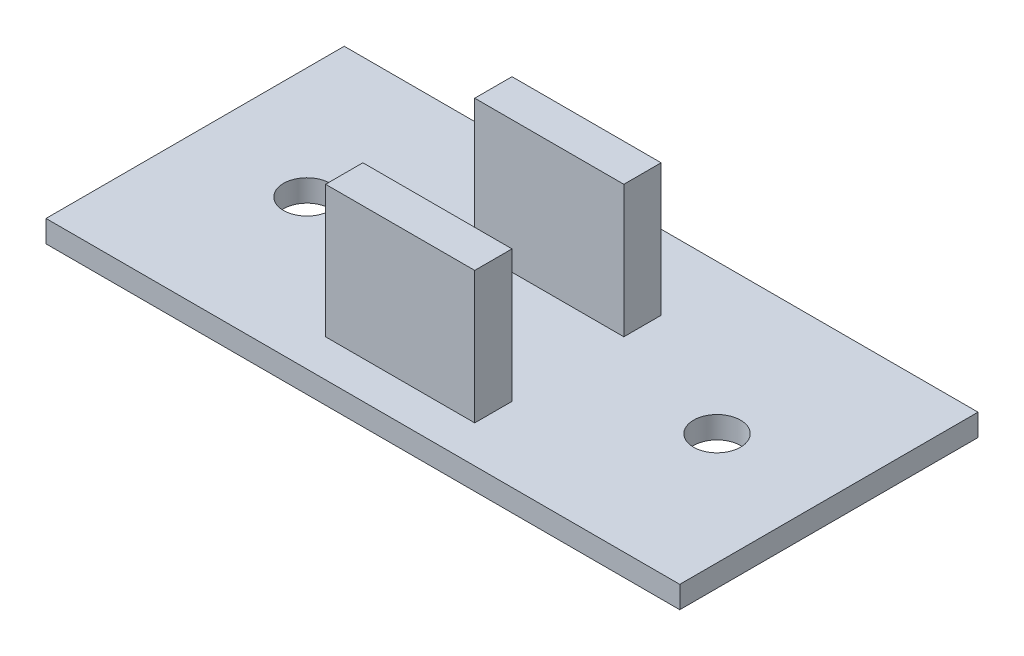
SolidWorks part; units mm, degrees
ref_plane "Front Plane" through (0, 0, 0) normal (0, 0, 1) x (1, 0, 0)
ref_plane "Top Plane" through (0, 0, 0) normal (0, 1, 0) x (1, 0, 0)
ref_plane "Right Plane" through (0, 0, 0) normal (1, 0, 0) x (0, 0, -1)
sketch "Sketch1" plane through (0, 0, 0) normal (0, 1, 0) x (1, 0, 0)
  line L0 (0, 10.16) -> (43.18, 10.16) construction
  line L1 (0, 0) -> (43.18, 0)
  line L2 (0, 0) -> (0, 20.32)
  line L3 (0, 20.32) -> (43.18, 20.32)
  line L4 (43.18, 0) -> (43.18, 20.32)
  line L5 (21.59, 20.32) -> (21.59, 0) construction
  circle A0 centre (7.62, 10.16) radius 1.6
  circle A1 centre (35.56, 10.16) radius 1.6
  dimension "D4" = 3.2
  dimension "D1" = 43.18
  dimension "D2" = 20.32
  dimension "D3" = 7.62
extrude "Boss-Extrude1" add sketch "Sketch1" along normal blind 1.5
sketch "Sketch2" plane through (0, 1.5, 0) normal (0, 1, 0) x (1, 0, 0)
  line L0 (0, 0) -> (43.18, 0) construction
  line L1 (16.51, 5.08) -> (26.67, 5.08)
  line L2 (16.51, 5.08) -> (16.51, 2.54)
  line L3 (16.51, 2.54) -> (26.67, 2.54)
  line L4 (26.67, 5.08) -> (26.67, 2.54)
  line L5 (16.51, 15.24) -> (16.51, 12.7)
  line L6 (16.51, 15.24) -> (26.67, 15.24)
  line L7 (26.67, 15.24) -> (26.67, 12.7)
  line L8 (16.51, 12.7) -> (26.67, 12.7)
  point P6 (21.59, 0)
  point P7 (21.59, 2.54)
  point P8 (16.51, 3.81)
  point P9 (16.51, 13.97)
  dimension "D1" = 2.54
  dimension "D2" = 2.54
  dimension "D3" = 10.16
  dimension "D5" = 10.16
  dimension "D4" = 2
extrude "Boss-Extrude2" add sketch "Sketch2" along normal blind 9 separate body
ref_plane "Plane1" through (0, 0, -3.81) normal (0, 0, -1) x (-1, 0, 0)
ref_plane "Plane2" through (21.59, 0, 0) normal (1, 0, 0) x (0, 0, -1)
equation "\"D1@Sketch1\"=17*2.54"
equation "\"D2@Sketch1\"=8*2.54"
equation "\"D3@Sketch1\"=3*2.54"
